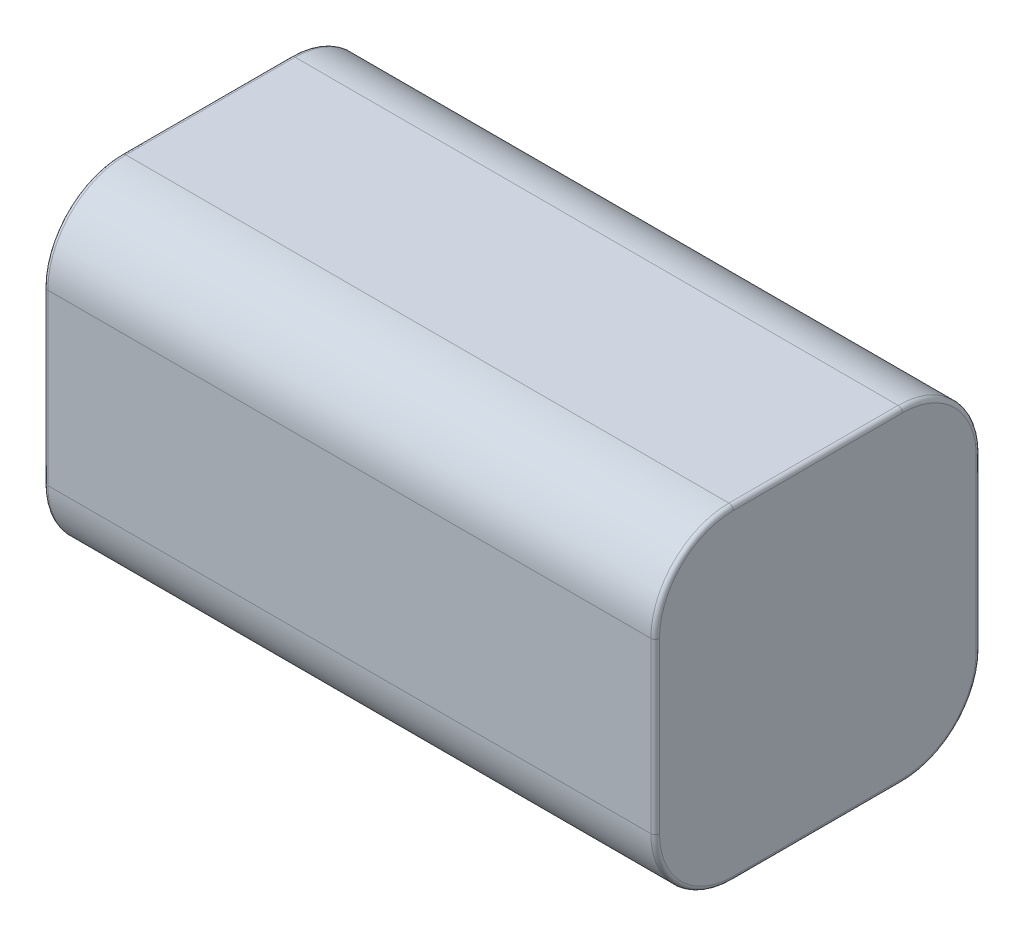
SolidWorks part; units mm, degrees
ref_plane "前视基准面" through (0, 0, 0) normal (0, 0, 1) x (1, 0, 0)
ref_plane "上视基准面" through (0, 0, 0) normal (0, 1, 0) x (1, 0, 0)
ref_plane "右视基准面" through (0, 0, 0) normal (1, 0, 0) x (0, 0, -1)
other "Configuration Table"
sketch "草图1" plane through (0, 0, 0) normal (1, 0, 0) x (0, 0, -1)
  line L0 (0, 0) -> (37.5, 0)
  line L1 (37.5, 0) -> (37.5, 37.5)
  line L2 (37.5, 37.5) -> (0, 37.5)
  line L3 (0, 37.5) -> (0, 0)
extrude "凸台-拉伸1" add sketch "草图1" along normal blind 70.5
fillet "圆角1" radius 9 4 edges at (35.25, 0, -37.5) (35.25, 0, 0) (35.25, 37.5, -37.5) (35.25, 37.5, 0)
fillet "圆角2" radius 0.5 16 edges at (0, 34.864, -34.864) (0, 37.5, -18.75) (0, 34.864, -2.636) (0, 18.75, 0) (0, 2.636, -2.636) (0, 0, -18.75) (0, 2.636, -34.864) (0, 18.75, -37.5) (70.5, 2.636, -2.636) (70.5, 18.75, 0) (70.5, 34.864, -2.636) (70.5, 37.5, -18.75) (70.5, 34.864, -34.864) (70.5, 18.75, -37.5) (70.5, 2.636, -34.864) (70.5, 0, -18.75)
